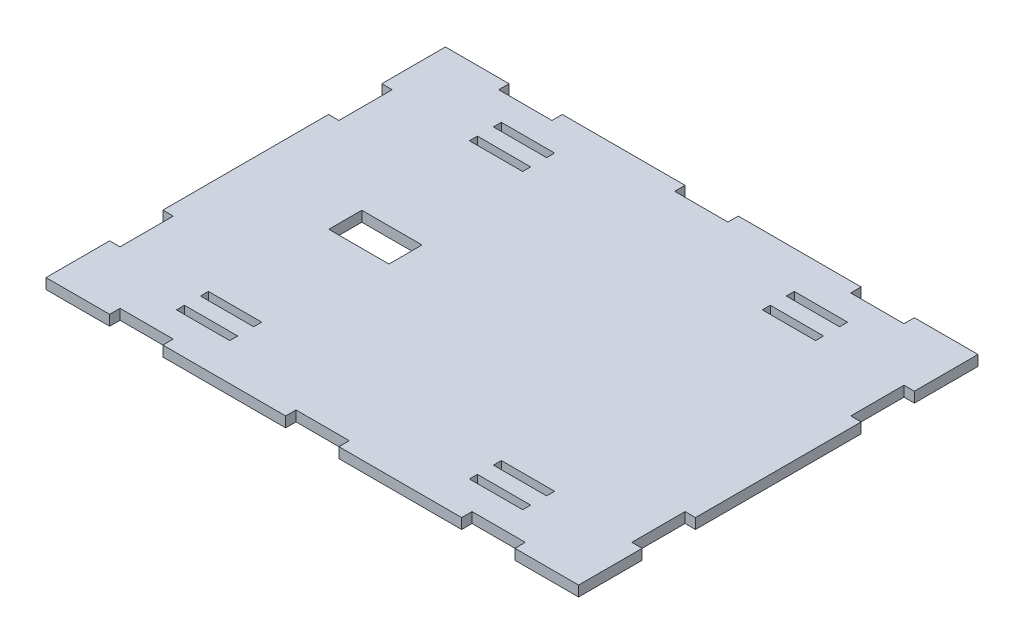
SolidWorks part; units mm, degrees
material "Very Low Density PE (SS)"
ref_plane "Front Plane" through (0, 0, 0) normal (0, 0, 1) x (1, 0, 0)
ref_plane "Top Plane" through (0, 0, 0) normal (0, 1, 0) x (1, 0, 0)
ref_plane "Right Plane" through (0, 0, 0) normal (1, 0, 0) x (0, 0, -1)
sketch "Sketch1" plane through (0, 0, 0) normal (0, 1, 0) x (1, 0, 0)
  line L0 (-125, 0) -> (125, 0) construction
  line L1 (-100, 75) -> (-76.1, 75)
  line L2 (-100, 75) -> (-100, 51.1)
  line L3 (-100, -75) -> (-76.1, -75)
  line L4 (100, 75) -> (100, 51.1)
  line L5 (0, 75) -> (0, -75) construction
  line L6 (-100, -55) -> (100, -55) construction
  line L11 (-65, -49) -> (-45, -49)
  line L12 (-65, -58) -> (-45, -58)
  line L25 (-65, -58) -> (-65, -61)
  line L32 (-65, -61) -> (-45, -61)
  line L33 (-45, -58) -> (-45, -61)
  line L34 (-45, -52) -> (-45, -49)
  line L35 (-65, -52) -> (-45, -52)
  line L36 (-65, -52) -> (-65, -49)
  line L37 (65, -61) -> (45, -61)
  line L38 (45, -58) -> (45, -61)
  line L39 (65, -58) -> (45, -58)
  line L40 (65, -58) -> (65, -61)
  line L41 (65, -52) -> (65, -49)
  line L42 (65, -52) -> (45, -52)
  line L43 (45, -52) -> (45, -49)
  line L44 (65, -49) -> (45, -49)
  line L45 (65, 52) -> (45, 52)
  line L46 (45, 52) -> (45, 49)
  line L47 (65, 49) -> (45, 49)
  line L48 (65, 52) -> (65, 49)
  line L49 (65, 58) -> (65, 61)
  line L50 (65, 58) -> (45, 58)
  line L51 (45, 58) -> (45, 61)
  line L52 (65, 61) -> (45, 61)
  line L53 (-65, 61) -> (-45, 61)
  line L54 (-45, 58) -> (-45, 61)
  line L55 (-65, 58) -> (-45, 58)
  line L56 (-65, 58) -> (-65, 61)
  line L57 (-65, 52) -> (-65, 49)
  line L58 (-65, 52) -> (-45, 52)
  line L59 (-45, 52) -> (-45, 49)
  line L60 (-65, 49) -> (-45, 49)
  line L61 (76.1, -71.1) -> (56.1, -71.1)
  line L63 (-76.1, -75) -> (-76.1, -71.1)
  line L64 (-76.1, -71.1) -> (-56.1, -71.1)
  line L65 (-56.1, -75) -> (-56.1, -71.1)
  line L66 (56.1, -75) -> (56.1, -71.1)
  line L68 (76.1, -75) -> (76.1, -71.1)
  line L69 (10, -75) -> (56.1, -75)
  line L70 (-10, -71.1) -> (10, -71.1)
  line L71 (-10, -71.1) -> (-10, -75)
  line L73 (10, -71.1) -> (10, -75)
  line L74 (-10, -71.1) -> (10, -75) construction
  line L75 (-10, -75) -> (10, -71.1) construction
  line L76 (-56.1, -75) -> (-10, -75)
  line L77 (76.1, -75) -> (100, -75)
  line L78 (76.1, 75) -> (76.1, 71.1)
  line L79 (56.1, 75) -> (56.1, 71.1)
  line L80 (76.1, 71.1) -> (56.1, 71.1)
  line L81 (10, 71.1) -> (10, 75)
  line L82 (-10, 71.1) -> (10, 71.1)
  line L83 (-10, 71.1) -> (-10, 75)
  line L84 (-56.1, 75) -> (-56.1, 71.1)
  line L85 (-76.1, 71.1) -> (-56.1, 71.1)
  line L86 (-76.1, 75) -> (-76.1, 71.1)
  line L87 (-10, 75) -> (0, 75) construction
  line L88 (10, 75) -> (56.1, 75)
  line L89 (0, 75) -> (10, 75) construction
  line L90 (-76.1, 75) -> (-56.1, 75) construction
  line L91 (-56.1, 75) -> (-10, 75)
  line L92 (56.1, 75) -> (76.1, 75) construction
  line L93 (76.1, 75) -> (100, 75)
  line L94 (100, -31.1) -> (96.1, -31.1)
  line L95 (100, 51.1) -> (96.1, 51.1)
  line L96 (100, 51.1) -> (100, 31.1) construction
  line L97 (100, 31.1) -> (96.1, 31.1)
  line L98 (96.1, 51.1) -> (96.1, 31.1)
  line L99 (96.1, -51.1) -> (96.1, -31.1)
  line L100 (100, -51.1) -> (96.1, -51.1)
  line L101 (100, -51.1) -> (100, -31.1) construction
  line L102 (100, 51.1) -> (100, 31.1) construction
  line L103 (100, 31.1) -> (100, -31.1)
  line L104 (100, -31.1) -> (100, -51.1) construction
  line L105 (100, -51.1) -> (100, -75)
  line L106 (-100, -31.1) -> (-96.1, -31.1)
  line L107 (-96.1, -51.1) -> (-96.1, -31.1)
  line L108 (-100, -51.1) -> (-96.1, -51.1)
  line L109 (-100, 31.1) -> (-96.1, 31.1)
  line L110 (-100, 51.1) -> (-96.1, 51.1)
  line L111 (-96.1, 51.1) -> (-96.1, 31.1)
  line L112 (-100, 51.1) -> (-100, 31.1) construction
  line L113 (-100, 31.1) -> (-100, -31.1)
  line L114 (-100, -31.1) -> (-100, -51.1) construction
  line L115 (-100, -51.1) -> (-100, -75)
  line L117 (-62.6, 6.2) -> (-40, 6.2)
  line L118 (-62.6, 6.2) -> (-62.6, -6.2)
  line L119 (-62.6, -6.2) -> (-40, -6.2)
  line L120 (-40, 6.2) -> (-40, -6.2)
  line L121 (-62.6, 6.2) -> (-40, -6.2) construction
  line L122 (-62.6, -6.2) -> (-40, 6.2) construction
  point P0 (0, 0)
  point P29 (0, 0)
  point P57 (0, -73.05)
  point P82 (-51.3, 0)
  dimension "D2" = 150
  dimension "D3" = 3
  dimension "D4" = 20
  dimension "D5" = 23.9
  dimension "D6" = 20
  dimension "D7" = 40
  dimension "D9" = 3
  dimension "D10" = 45
  dimension "D11" = 20
  dimension "D12" = 3.9
  dimension "D13" = 20
  dimension "D14" = 12.4
  dimension "D15" = 23.9
  dimension "D16" = 20
  dimension "D17" = 3.9
  dimension "D18" = 200
  dimension "D19" = 22.6
extrude "Boss-Extrude1" add sketch "Sketch1" along normal blind 3.9
